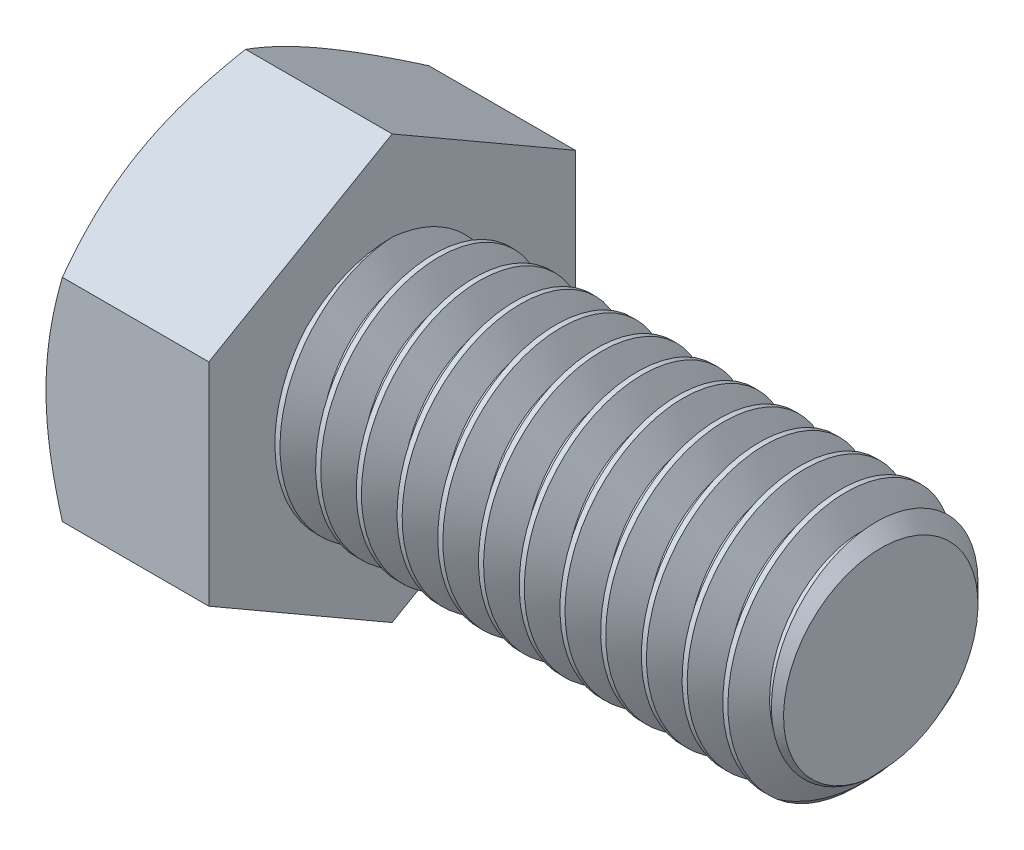
SolidWorks part; units mm, degrees
ref_plane "Front Plane" through (0, 0, 0) normal (0, 0, 1) x (1, 0, 0)
ref_plane "Top Plane" through (0, 0, 0) normal (0, 1, 0) x (1, 0, 0)
ref_plane "Right Plane" through (0, 0, 0) normal (1, 0, 0) x (0, 0, -1)
sketch "Sketch1" plane through (0, 0, 0) normal (0, 0, 1) x (1, 0, 0)
  line L0 (-12.7, 0) -> (12.7, 0) construction
  line L1 (12.7, 4.7625) -> (12.7, -4.7625) construction
  line L2 (-6.35, 7.1438) -> (-6.35, -7.1438) construction
  line L3 (-12.7, 7.1437) -> (-12.7, -7.1437) construction
  point P9 (-6.35, 0)
  point P10 (7.1437, -4.7625)
  dimension "D1" = 5.5562
  dimension "Screw Dia" = 9.525
  dimension "Hex" = 14.2875
  dimension "Head Ht" = 6.35
  dimension "Screw Lenght" = 19.05
ref_plane "Plane2" through (12.7, 0, 0) normal (1, 0, 0) x (0, 0, -1)
sketch "Sketch5" plane through (12.7, 0, 0) normal (1, 0, 0) x (0, 0, -1)
  circle A0 centre (0, 0) radius 4.7625
extrude "Boss-Extrude3" add sketch "Sketch5" against normal up to vertex (19.05 mm away) up to point (-6.35, 0, 0)
sketch "Sketch9" plane through (12.7, 0, 0) normal (1, 0, 0) x (0, 0, -1)
  circle A1 centre (0, 0) radius 4.7625
  circle A2 centre (0, 0) radius 4.7625
  dimension "D1" = 0
curve "Helix/Spiral1" pitch 1.5875 height 20.6375 turns 13 parameters "Pitch"=1.5875
chamfer "Chamfer1" distance 0.9715 angle 45 1 edges at (12.7, 0, -4.7625)
sketch "Sketch10" plane through (0, 0, 0) normal (0, 0, 1) x (1, 0, 0)
  line L0 (12.7, 4.7625) -> (13.2953, 3.7314)
  line L1 (13.2953, 3.7314) -> (13.4937, 3.7314)
  line L2 (13.4937, 3.7314) -> (14.0891, 4.7625)
  line L3 (12.7, 4.7625) -> (14.0891, 4.7625)
  line L4 (13.3945, 4.7625) -> (13.3945, 3.7314) construction
  line L5 (12.9977, 4.2469) -> (13.7914, 4.2469) construction
  dimension "D1" = 60
  dimension "D2" = 0.1984
  dimension "D3" = 0.7937
sweep "Cut-Sweep1" cut profiles "Sketch10" path "Helix/Spiral1"
sketch "Sketch6" plane through (-6.35, 0, 0) normal (-1, 0, 0) x (0, 0, 1)
  line L0 (0, 7.1438) -> (0, -7.1438) construction
  line L1 (7.1437, 4.1244) -> (0, 8.2489)
  line L2 (0, 8.2489) -> (-7.1438, 4.1244)
  line L3 (-7.1438, 4.1244) -> (-7.1438, -4.1244)
  line L4 (-7.1438, -4.1244) -> (0, -8.2489)
  line L5 (0, -8.2489) -> (7.1438, -4.1244)
  line L6 (7.1438, -4.1244) -> (7.1437, 4.1244)
  circle A0 centre (0, 0) radius 7.1438 construction
extrude "Boss-Extrude4" add sketch "Sketch6" along normal up to vertex (6.35 mm away) up to point (-12.7, -7.1437, 0)
sketch "Sketch7" plane through (-12.7, 0, 0) normal (-1, 0, 0) x (0, 0, 1)
  circle A0 centre (0, 0) radius 7.1438 construction
  circle A1 centre (0, 0) radius 7.1438
sketch "Sketch8" plane through (-12.7, 0, 0) normal (-1, 0, 0) x (0, 0, 1)
  circle A0 centre (0, 0) radius 7.1438 construction
  circle A1 centre (0, 0) radius 7.1438
extrude "Cut-Extrude3" cut sketch "Sketch8" against normal through all draft 60 flip side to cut
sketch "Sketch12" plane through (-12.7, 0, 0) normal (-1, 0, 0) x (0, 0, 1)
  line L0 (0, 5.5007) -> (0, 3.0718) construction
  line L1 (0.2143, 5.5007) -> (0.2143, 3.0718)
  line L2 (-0.2143, 5.5007) -> (-0.2143, 3.0718)
  line L3 (0, 4.7625) -> (0, -4.7625) construction
  arc A0 (0.2143, 5.5007) -> (-0.2143, 5.5007) centre (0, 5.5007) ccw
  arc A1 (-0.2143, 3.0718) -> (0.2143, 3.0718) centre (0, 3.0718) ccw
  circle A3 centre (0, 0) radius 2.8575 construction
  circle A4 centre (0, 0) radius 5.715 construction
  point P2 (0, 4.2862)
  dimension "D1" = 5.715
  dimension "D3" = 11.43
  dimension "D2" = 0.4286
extrude "Cut-Extrude4" cut sketch "Sketch12" against normal blind 0.254
pattern_circular "CirPattern1" count 3 over 360 about axis through (0, 0, 0) along (1, 0, 0) of "Cut-Extrude4"
equation "\"D2@Sketch10\" = \"Pitch@Helix/Spiral1\"*.125"
equation "\"D3@Sketch10\" = \"Pitch@Helix/Spiral1\"*.5"
equation "\"D1@Chamfer1\" = \"Pitch@Helix/Spiral1\"*.612"
equation "\"D1@Sketch12\" = \"Hex@Sketch1\"*.4"
equation "\"D3@Sketch12\" = \"Hex@Sketch1\"*.8"
equation "\"D2@Sketch12\" = \"Hex@Sketch1\"*.03"
equation "\"D1@Sketch1\" = \"Pitch@Helix/Spiral1\"*3.5"
equation "\"D3@Helix/Spiral1\" = \"Screw Lenght@Sketch1\"+\"Pitch@Helix/Spiral1\""
